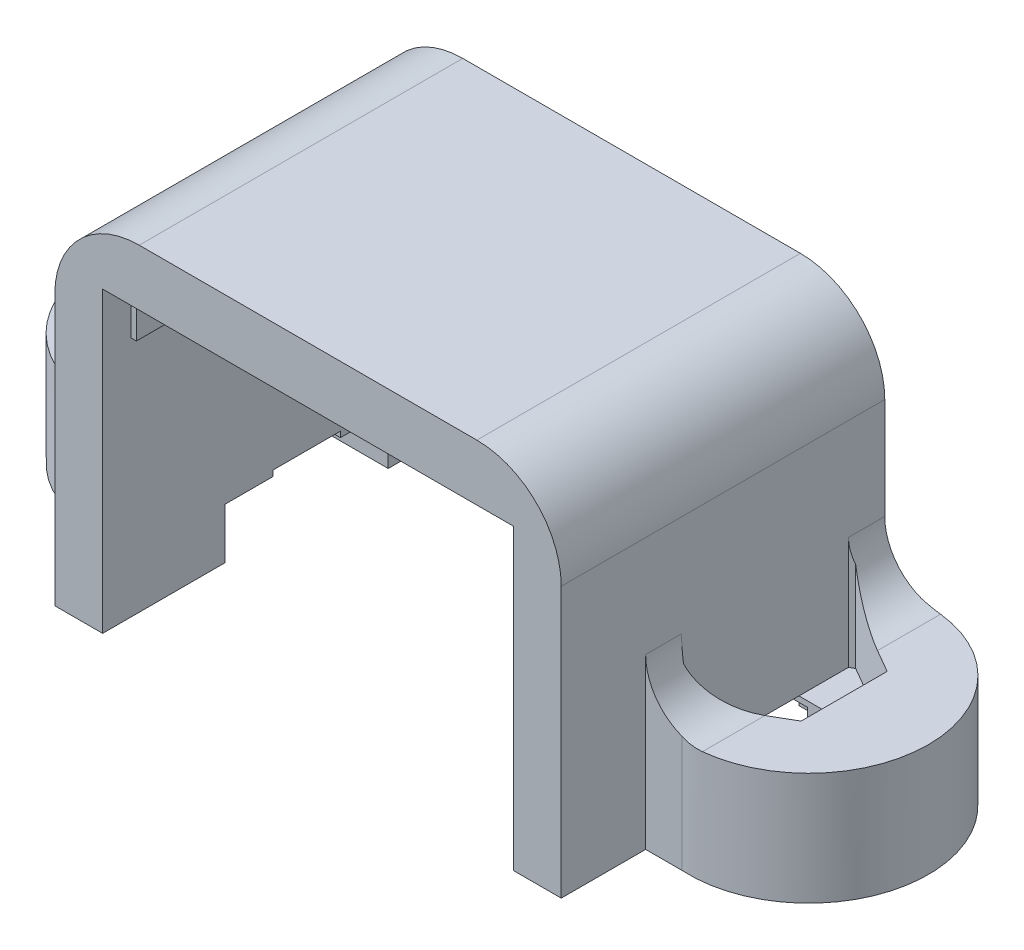
SolidWorks part; units mm, degrees
material "Polyester Resin"
ref_plane "Front Plane" through (0, 0, 0) normal (0, 0, 1) x (1, 0, 0)
ref_plane "Top Plane" through (0, 0, 0) normal (0, 1, 0) x (1, 0, 0)
ref_plane "Right Plane" through (0, 0, 0) normal (1, 0, 0) x (0, 0, -1)
sketch "Sketch1" plane through (0, 0, 0) normal (0, 0, 1) x (1, 0, 0)
  line L0 (0, 0) -> (0, 14.1376) construction
  line L1 (-9, 0) -> (9, 0) construction
  line L2 (-9, 0) -> (-9, 9.6)
  line L3 (-6, 12.6) -> (6, 12.6)
  line L4 (9, 0) -> (9, 9.6)
  line L5 (-9, 0) -> (-7.3, 0)
  line L6 (-7.3, 0) -> (-7.3, 10.6)
  line L7 (-7.3, 10.6) -> (7.3, 10.6)
  line L8 (7.3, 10.6) -> (7.3, 0)
  line L9 (7.3, 0) -> (9, 0)
  arc A0 (6, 12.6) -> (9, 9.6) centre (6, 9.6) cw
  arc A1 (-9, 9.6) -> (-6, 12.6) centre (-6, 9.6) cw
  point P13 (9, 12.6)
  point P16 (-9, 12.6)
  dimension "D5" = 3
  dimension "D1" = 2
  dimension "D2" = 18
  dimension "D3" = 14.6
  dimension "D4" = 10.6
extrude "Boss-Extrude1" add sketch "Sketch1" along normal mid plane 11.5
ref_plane "Plane1" through (0, 0, 4.75) normal (0, 0, 1) x (1, 0, 0)
sketch "Sketch2" plane through (0, 0, 4.75) normal (0, 0, 1) x (1, 0, 0)
  line L3 (-5.3, 10.6) -> (-5.3, 10.4)
  line L4 (-5.3, 10.4) -> (-6.6, 10.4)
  line L5 (-7.3, 0) -> (-7.3, 10.6)
  line L6 (-7.3, 10.6) -> (7.3, 10.6)
  line L7 (-7.3, 8.6) -> (-7.3, 10.6)
  line L8 (-7.3, 10.6) -> (-5.3, 10.6)
  line L9 (-7.1, 9.9) -> (-7.1, 8.6)
  line L10 (-7.1, 8.6) -> (-7.3, 8.6)
  line L11 (0, 10.6) -> (0, -1.0484) construction
  line L12 (-7.3, 10.6) -> (7.3, 10.6) construction
  line L13 (7.1, 8.6) -> (7.3, 8.6)
  line L14 (5.3, 10.6) -> (5.3, 10.4)
  line L15 (7.3, 10.6) -> (5.3, 10.6)
  line L16 (5.3, 10.4) -> (6.6, 10.4)
  line L17 (7.1, 9.9) -> (7.1, 8.6)
  line L18 (7.3, 8.6) -> (7.3, 10.6)
  arc A0 (-6.6, 10.4) -> (-7.1, 9.9) centre (-6.6, 9.9) ccw
  arc A1 (6.6, 10.4) -> (7.1, 9.9) centre (6.6, 9.9) cw
  dimension "D6" = 0.5
  dimension "D2" = 0.2
  dimension "D3" = 0.2
  dimension "D4" = 2
  dimension "D5" = 2
  dimension "D1" = 0
extrude "Boss-Extrude2" add sketch "Sketch2" against normal blind 4
ref_plane "Plane2" through (0, 0, -0.25) normal (0, 0, -1) x (-1, 0, 0)
sketch "Sketch3" plane through (0, 0, -0.25) normal (0, 0, -1) x (-1, 0, 0)
  line L29 (7.3, 8.6) -> (7.3, 10.6)
  line L30 (7.3, 10.6) -> (5.3, 10.6)
  line L31 (5.3, 10.6) -> (5.3, 10.4)
  line L32 (5.3, 10.4) -> (6.6, 10.4)
  line L33 (7.1, 9.9) -> (7.1, 8.6)
  line L34 (7.1, 8.6) -> (7.3, 8.6)
  line L35 (7.3, 8.6) -> (7.3, 10.6)
  line L36 (7.3, 10.6) -> (5.3, 10.6)
  line L37 (5.3, 10.6) -> (5.3, 10.4)
  line L38 (5.3, 10.4) -> (6.6, 10.4)
  line L39 (7.1, 9.9) -> (7.1, 8.6)
  line L40 (7.1, 8.6) -> (7.3, 8.6)
  line L68 (-7.1, 8.6) -> (-7.1, 9.9)
  line L69 (-7.3, 8.6) -> (-7.1, 8.6)
  line L70 (-7.3, 10.6) -> (-7.3, 8.6)
  line L71 (-5.3, 10.6) -> (-7.3, 10.6)
  line L72 (-5.3, 10.4) -> (-5.3, 10.6)
  line L73 (-6.6, 10.4) -> (-5.3, 10.4)
  line L74 (-7.1, 8.6) -> (-7.1, 9.9)
  line L75 (-7.3, 8.6) -> (-7.1, 8.6)
  line L76 (-7.3, 10.6) -> (-7.3, 8.6)
  line L77 (-5.3, 10.6) -> (-7.3, 10.6)
  line L78 (-5.3, 10.4) -> (-5.3, 10.6)
  line L79 (-6.6, 10.4) -> (-5.3, 10.4)
  arc A6 (7.1, 9.9) -> (6.6, 10.4) centre (6.6, 9.9) ccw
  arc A7 (7.1, 9.9) -> (6.6, 10.4) centre (6.6, 9.9) ccw
  arc A9 (-6.6, 10.4) -> (-7.1, 9.9) centre (-6.6, 9.9) ccw
  arc A10 (-6.6, 10.4) -> (-7.1, 9.9) centre (-6.6, 9.9) ccw
  dimension "D1" = 0
  dimension "D2" = 0
extrude "Boss-Extrude3" add sketch "Sketch3" along normal blind 2
ref_plane "Plane3" through (0, 0, -3.25) normal (0, 0, -1) x (-1, 0, 0)
sketch "Sketch4" plane through (0, 0, -3.25) normal (0, 0, -1) x (-1, 0, 0)
  line L185 (5.3, 10.6) -> (5.3, 10.4)
  line L186 (7.3, 10.6) -> (5.3, 10.6)
  line L187 (7.3, 8.6) -> (7.3, 10.6)
  line L188 (7.1, 8.6) -> (7.3, 8.6)
  line L189 (5.3, 10.4) -> (6.6, 10.4)
  line L190 (7.1, 9.9) -> (7.1, 8.6)
  line L191 (-5.3, 10.4) -> (5.3, 10.4)
  line L192 (7.3, 10.6) -> (5.3, 10.6)
  line L193 (7.3, 8.6) -> (7.3, 10.6)
  line L194 (7.1, 8.6) -> (7.3, 8.6)
  line L195 (5.3, 10.4) -> (6.6, 10.4)
  line L196 (7.1, 9.9) -> (7.1, 8.6)
  line L216 (-5.3, 10.6) -> (5.3, 10.6)
  line L222 (-7.3, 8.6) -> (-7.1, 8.6)
  line L223 (-7.1, 8.6) -> (-7.1, 9.9)
  line L224 (-7.3, 10.6) -> (-7.3, 8.6)
  line L225 (-5.3, 10.4) -> (-5.3, 10.6)
  line L226 (-5.3, 10.6) -> (-7.3, 10.6)
  line L227 (-6.6, 10.4) -> (-5.3, 10.4)
  line L228 (-7.3, 8.6) -> (-7.1, 8.6)
  line L229 (-7.1, 8.6) -> (-7.1, 9.9)
  line L230 (-7.3, 10.6) -> (-7.3, 8.6)
  line L232 (-5.3, 10.6) -> (-7.3, 10.6)
  line L233 (-6.6, 10.4) -> (-5.3, 10.4)
  arc A32 (7.1, 9.9) -> (6.6, 10.4) centre (6.6, 9.9) ccw
  arc A33 (7.1, 9.9) -> (6.6, 10.4) centre (6.6, 9.9) ccw
  arc A37 (-6.6, 10.4) -> (-7.1, 9.9) centre (-6.6, 9.9) ccw
  arc A38 (-6.6, 10.4) -> (-7.1, 9.9) centre (-6.6, 9.9) ccw
  dimension "D1" = 0
  dimension "D2" = 0
extrude "Boss-Extrude4" add sketch "Sketch4" along normal up to surface (2.5 mm away) up to face at (0, 6.6843, -5.75)
sketch "Sketch6" plane through (0, 0, 0) normal (0, -1, 0) x (1, 0, 0)
  line L0 (-9, -5.75) -> (-10.2988, -5.75)
  line L1 (-9, -5.75) -> (-9, 2.75)
  line L7 (-9, 2.75) -> (-10.2988, 2.75)
  line L8 (-9, 5.75) -> (-9, -5.75) construction
  line L9 (-14.8, -1.5) -> (-5.8172, -1.5) construction
  arc A0 (-10.2988, 2.75) -> (-10.2988, -5.75) centre (-10.543, -1.5) ccw
  dimension "D1" = 8.5
  dimension "D2" = 5.8
extrude "Boss-Extrude5" add sketch "Sketch6" against normal blind 4
sketch "Sketch7" plane through (0, 4, 0) normal (0, 1, 0) x (1, 0, 0)
  line L0 (-9, -1.4736) -> (-9, 4.4592)
  line L1 (-9.1621, 4.5527) -> (-11.8121, 3.0228)
  line L2 (-11.8121, 3.0228) -> (-11.8121, -0.0372)
  line L3 (-11.8121, -0.0372) -> (-9.1621, -1.5672)
  line L4 (-9.1621, -1.5672) -> (-9, -1.4736)
  line L6 (-9, 4.4592) -> (-9.1621, 4.5527)
  line L7 (-9, 5.75) -> (-9, -2.75) construction
  line L9 (-6.5121, -0.0372) -> (-6.5121, 1.4928) [skipped]
  circle A0 centre (-9.1621, 1.4928) radius 2.65 construction
  dimension "D1" = 5.3
extrude "Cut-Extrude1" cut sketch "Sketch7" against normal blind 2
mirror "Mirror1" about plane through (0, 0, 0) normal (1, 0, 0) of "Boss-Extrude5", "Cut-Extrude1"
sketch "Sketch9" plane through (0, 2, 0) normal (0, 1, 0) x (1, 0, 0)
  line L0 (-14.8, 1.5) -> (14.8, 1.5) construction
  line L1 (0, 0) -> (0, 8.4199) construction
  line L2 (-10, 2.7) -> (10, 2.7)
  line L4 (-10, 0.3) -> (10, 0.3)
  arc A0 (-10.2988, 5.75) -> (-10.2988, -2.75) centre (-10.543, 1.5) ccw construction
  arc A1 (10.2988, -2.75) -> (10.2988, 5.75) centre (10.543, 1.5) ccw construction
  arc A2 (-10, 2.7) -> (-10, 0.3) centre (-10, 1.5) ccw
  arc A3 (10, 2.7) -> (10, 0.3) centre (10, 1.5) cw
  dimension "D2" = 10
  dimension "D1" = 2.4
extrude "Cut-Extrude2" cut sketch "Sketch9" against normal blind 8
fillet "Fillet1" radius 2 4 edges at (-9, 4, 2.1118) (-9, 4, -5.1046) (9, 4, 2.1118) (9, 4, -5.1046)
sketch "Sketch11" plane through (-7.3, 0, 0) normal (1, 0, 0) x (0, 0, -1)
  line L0 (-2.757, 0) -> (5.757, 0) construction
  line L2 (-1.4, 0) -> (4.4, 0)
  line L3 (-1.4, 0) -> (-1.4, 1.8)
  line L4 (-1.4, 1.8) -> (4.4, 1.8)
  line L5 (4.4, 0) -> (4.4, 1.8)
  line L7 (0.3, 0) -> (0.3, 2) construction
  line L9 (2.7, 2) -> (2.7, 0) construction
  line L10 (0.3, 2) -> (2.7, 2) construction
  dimension "D1" = 1.7
  dimension "D2" = 1.7
  dimension "D3" = 0.2
extrude "Cut-Extrude15" cut sketch "Sketch11" against normal blind 2
mirror "Mirror2" about plane through (0, 0, 0) normal (1, 0, 0) of "Cut-Extrude15"
